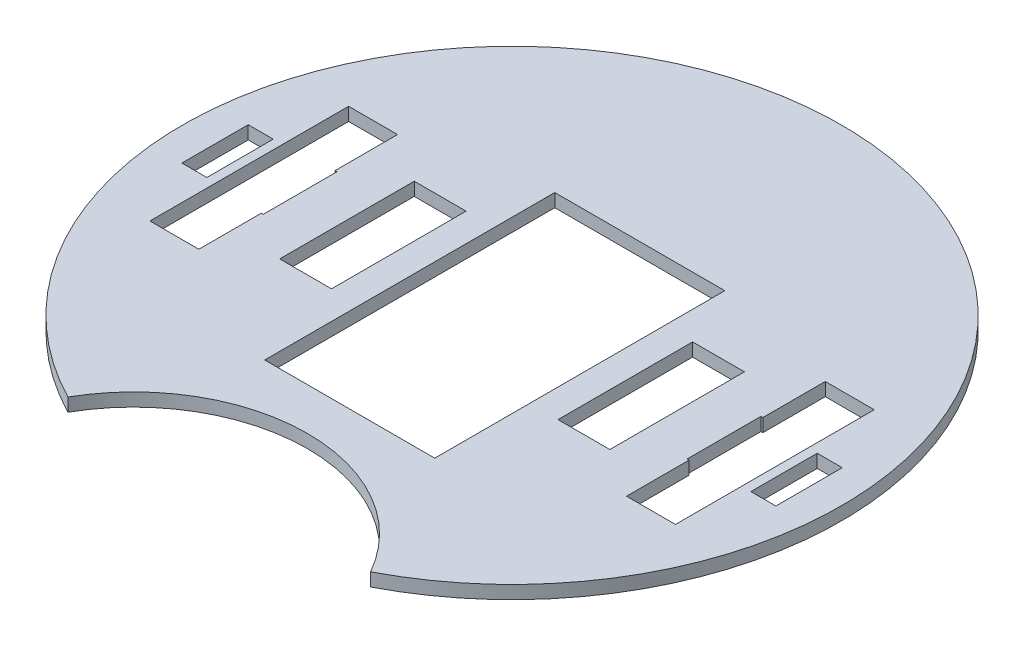
SolidWorks part; units mm, degrees
ref_plane "Front Plane" through (0, 0, 0) normal (0, 0, 1) x (1, 0, 0)
ref_plane "Top Plane" through (0, 0, 0) normal (0, 1, 0) x (1, 0, 0)
ref_plane "Right Plane" through (0, 0, 0) normal (1, 0, 0) x (0, 0, -1)
sketch "Sketch1" plane through (0, 0, 0) normal (0, 1, 0) x (1, 0, 0)
  line L0 (0, -83.2398) -> (-33.2911, -64.4046) construction
  line L1 (0, -83.2398) -> (0, 0) construction
  arc A0 (33.2911, -64.4046) -> (-33.2911, -64.4046) centre (0, 0) ccw
  arc A1 (33.2911, -64.4046) -> (-33.2911, -64.4046) centre (0, -83.2398) ccw
  dimension "D1" = 145
  dimension "D2" = 76.5
  dimension "D3" = 60.5
extrude "Boss-Extrude1" add sketch "Sketch1" along normal blind 2.9
sketch "solenoid placement" plane through (0, 2.9, 0) normal (0, 1, 0) x (1, 0, 0)
  line L0 (0, 0) -> (0, -36) construction
  line L1 (0, -36) -> (0, -44.9898) construction
  line L2 (-19, -36) -> (19, -36) construction
  line L3 (-19, -36) -> (-19, 28.4) construction
  line L4 (-19, 28.4) -> (19, 28.4) construction
  line L5 (19, -36) -> (19, 28.4) construction
  line L6 (-18.7, 28.1) -> (18.7, 28.1)
  line L7 (18.7, -35.7) -> (18.7, 28.1)
  line L8 (-18.7, -35.7) -> (18.7, -35.7)
  line L9 (-18.7, -35.7) -> (-18.7, 28.1)
  circle A1 centre (0, 0) radius 72.5 construction
  arc A2 (33.2911, -64.4046) -> (-33.2911, -64.4046) centre (0, 0) ccw construction
  arc A3 (33.2911, -64.4046) -> (-33.2911, -64.4046) centre (0, -83.2398) ccw construction
  dimension "D1" = 64.4
  dimension "D2" = 36
  dimension "D3" = 0.3
  dimension "D4" = 38
extrude "Cut-Extrude1" cut sketch "solenoid placement" against normal through all
sketch "Sketch2" plane through (0, 2.9, 0) normal (0, 1, 0) x (1, 0, 0)
  line L0 (47.34, -21.5538) -> (47.34, 21.5538) construction
  line L1 (-57.5, -21.5538) -> (-47.34, -21.5538) construction
  line L2 (-57.5, -21.5538) -> (-57.5, 21.5538) construction
  line L3 (-57.5, 21.5538) -> (-47.34, 21.5538) construction
  line L4 (-47.34, -21.5538) -> (-47.34, 21.5538) construction
  line L5 (57.5, 21.5538) -> (47.34, 21.5538) construction
  line L6 (57.5, -21.5538) -> (57.5, 21.5538) construction
  line L7 (57.5, -21.5538) -> (47.34, -21.5538) construction
  line L8 (57.8, -21.8538) -> (57.8, 21.8538)
  line L9 (57.8, -21.8538) -> (47.04, -21.8538)
  line L10 (47.04, -21.8538) -> (47.04, 21.8538)
  line L11 (57.8, 21.8538) -> (47.04, 21.8538)
  line L12 (0, 0) -> (0, 72.5) construction
  line L13 (-57.8, 21.8538) -> (-47.04, 21.8538)
  line L14 (-47.04, -21.8538) -> (-47.04, 21.8538)
  line L15 (-57.8, -21.8538) -> (-47.04, -21.8538)
  line L16 (-57.8, -21.8538) -> (-57.8, 21.8538)
  arc A0 (33.2911, -64.4046) -> (-33.2911, -64.4046) centre (0, 0) ccw construction
extrude "Cut-Extrude2" cut sketch "Sketch2" against normal through all
sketch "Sketch3" plane through (0, 2.9, 0) normal (0, 1, 0) x (1, 0, 0)
  line L0 (-36.31, -14.8) -> (-24.91, -14.8)
  line L1 (-36.51, -15) -> (-24.71, -15) construction
  line L2 (-36.51, -15) -> (-36.51, 15) construction
  line L3 (-36.51, 15) -> (-24.71, 15) construction
  line L4 (-24.71, -15) -> (-24.71, 15) construction
  line L5 (-24.91, -14.8) -> (-24.91, 14.8)
  line L6 (-36.31, 14.8) -> (-24.91, 14.8)
  line L7 (-36.31, -14.8) -> (-36.31, 14.8)
  line L8 (0, 0) -> (0, 72.5) construction
  line L9 (24.71, -15) -> (24.71, 15) construction
  line L10 (36.51, 15) -> (24.71, 15) construction
  line L11 (36.51, -15) -> (36.51, 15) construction
  line L12 (36.51, -15) -> (24.71, -15) construction
  line L13 (36.31, -14.8) -> (36.31, 14.8)
  line L14 (36.31, 14.8) -> (24.91, 14.8)
  line L15 (24.91, -14.8) -> (24.91, 14.8)
  line L16 (36.31, -14.8) -> (24.91, -14.8)
  arc A0 (33.2911, -64.4046) -> (-33.2911, -64.4046) centre (0, 0) ccw construction
  dimension "D1" = 0.2
extrude "Cut-Extrude3" cut sketch "Sketch3" against normal through all
sketch "Sketch5" plane through (0, 2.9, 0) normal (0, 1, 0) x (1, 0, 0)
  line L1 (-65.33, 7.3) -> (-59.83, 7.3)
  line L2 (-65.53, 7.5) -> (-59.63, 7.5) construction
  line L3 (-65.53, 7.5) -> (-65.53, -7.5) construction
  line L4 (-65.53, -7.5) -> (-59.63, -7.5) construction
  line L6 (-59.63, 7.5) -> (-59.63, -7.5) construction
  line L7 (-59.83, 7.3) -> (-59.83, -7.3)
  line L8 (-65.33, -7.3) -> (-59.83, -7.3)
  line L9 (-65.33, 7.3) -> (-65.33, -7.3)
  line L10 (59.63, 7.5) -> (59.63, -7.5) construction
  line L11 (65.53, -7.5) -> (59.63, -7.5) construction
  line L12 (65.53, 7.5) -> (65.53, -7.5) construction
  line L13 (65.53, 7.5) -> (59.63, 7.5) construction
  line L14 (65.33, 7.3) -> (65.33, -7.3)
  line L15 (65.33, -7.3) -> (59.83, -7.3)
  line L28 (0, 0) -> (0, 72.5) construction
  line L29 (59.83, 7.3) -> (59.83, -7.3)
  line L30 (65.33, 7.3) -> (59.83, 7.3)
  arc A0 (33.2911, -64.4046) -> (-33.2911, -64.4046) centre (0, 0) ccw construction
  dimension "D1" = 0.2
extrude "Cut-Extrude4" cut sketch "Sketch5" against normal through all
sketch "Sketch6" plane through (0, 2.9, 0) normal (0, 1, 0) x (1, 0, 0)
  line L0 (-47.04, -21.8538) -> (-47.04, 21.8538) construction
  line L1 (-47.04, 7.8128) -> (-46.91, 7.8128) construction
  line L2 (-47.04, 7.8128) -> (-47.04, -7.8128) construction
  line L3 (-47.04, -7.8128) -> (-46.91, -7.8128) construction
  line L4 (-46.91, 7.8128) -> (-46.91, -7.8128) construction
  line L9 (-47.34, 8.1128) -> (-46.61, 8.1128)
  line L10 (-46.61, 8.1128) -> (-46.61, -8.1128)
  line L11 (-47.34, -8.1128) -> (-46.61, -8.1128)
  line L12 (-47.34, 8.1128) -> (-47.34, -8.1128)
  line L13 (0, 0) -> (0, 72.5) construction
  line L14 (46.91, 7.8128) -> (46.91, -7.8128) construction
  line L15 (47.04, -7.8128) -> (46.91, -7.8128) construction
  line L16 (47.04, 7.8128) -> (47.04, -7.8128) construction
  line L17 (47.04, 7.8128) -> (46.91, 7.8128) construction
  line L18 (47.34, 8.1128) -> (47.34, -8.1128)
  line L19 (47.34, -8.1128) -> (46.61, -8.1128)
  line L20 (46.61, 8.1128) -> (46.61, -8.1128)
  line L21 (47.34, 8.1128) -> (46.61, 8.1128)
  arc A0 (33.2911, -64.4046) -> (-33.2911, -64.4046) centre (0, 0) ccw construction
extrude "Cut-Extrude5" cut sketch "Sketch6" against normal through all
equation "\"smallPulleyTeeth\"= 15"
equation "\"largePulleyTeeth\"= 30"
equation "\"eighthThick\"= 2.9mm"
equation "\"sixteenthThick\" = 1.7mm"
equation "\"quarterThick\"=5.9mm"
equation "\"OD\" = 145mm"
equation "\"puckAngle\" = 60.5deg"
equation "\"D1@Sketch1\"=\"OD\""
equation "\"puckDiam\" = 76.5mm"
equation "\"D2@Sketch1\"=\"puckDiam\""
equation "\"D3@Sketch1\"=\"puckAngle\""
equation "\"D1@Boss-Extrude1\"=\"eighthThick\""
equation "\"axlePress\" = 5.9mm"
equation "\"press\" = 0.2mm"
equation "\"D1@Sketch3\"=\"press\""
equation "\"wheelClear\" = 0.3mm"
equation "\"D1@Sketch2\"=\"wheelClear\""
equation "\"D1@Sketch6\"=\"wheelClear\""
equation "\"D1@Sketch5\"=\"press\""
